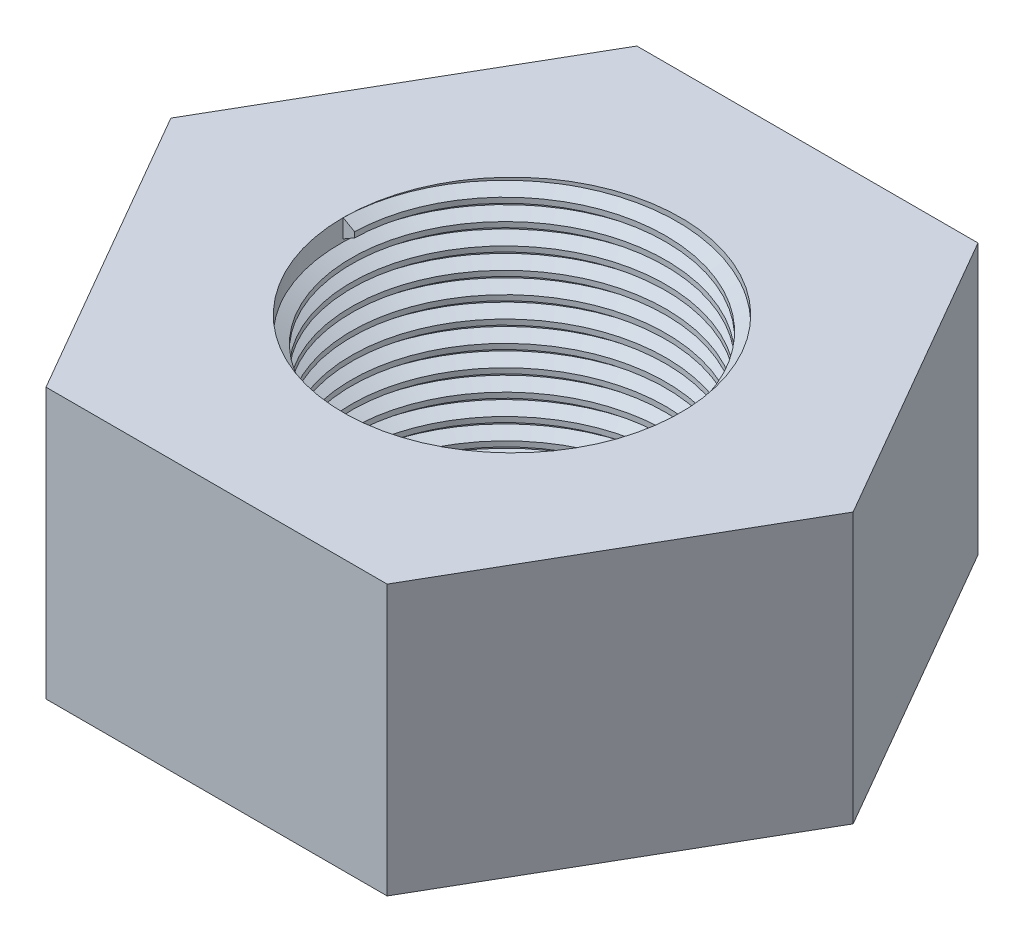
SolidWorks part; units mm, degrees
ref_plane "Ebene vorne" through (0, 0, 0) normal (0, 0, 1) x (1, 0, 0)
ref_plane "Ebene oben" through (0, 0, 0) normal (0, 1, 0) x (1, 0, 0)
ref_plane "Ebene rechts" through (0, 0, 0) normal (1, 0, 0) x (0, 0, -1)
sketch "Skizze1" plane through (0, 0, 0) normal (0, 1, 0) x (1, 0, 0)
  line L1 (4.0415, 0) -> (2.0207, 3.5)
  line L2 (2.0207, 3.5) -> (-2.0207, 3.5)
  line L3 (-2.0207, 3.5) -> (-4.0415, 0)
  line L4 (-4.0415, 0) -> (-2.0207, -3.5)
  line L5 (-2.0207, -3.5) -> (2.0207, -3.5)
  line L6 (2.0207, -3.5) -> (4.0415, 0)
  circle A0 centre (0, 0) radius 3.5 construction
  point P1 (0, 0)
  dimension "D1" = 7
extrude "Aufsatz-Linear austragen1" add sketch "Skizze1" along normal blind 3.2
sketch "Skizze2" plane through (0, 3.2, 0) normal (0, 1, 0) x (1, 0, 0)
  circle A0 centre (0, 0) radius 2
  dimension "D1" = 4
extrude "Schnitt-Linear austragen1" cut sketch "Skizze2" against normal up to surface (3.2 mm away) up to face at (0, 0, 0)
thread "Gewinde1" pitch 0.25 method extrude profile "Gewindeprofil1" start angle 0, offset 0, length 0, pitch 0.25, diameter 4
ref_plane "Ebene4" through (-2, 3.2, 0) normal (0, 0, 1) x (-1, 0, 0)
sketch "Gewindeprofil1" plane through (-2, 3.2, 0) normal (0, 0, 1) x (-1, 0, 0)
  line L0 (0, 0) -> (0, 0.25) construction
  line L11 (0, 0) -> (0, 0.2187)
  line L12 (0, 0.2187) -> (-0.1353, 0.1406)
  line L13 (-0.1353, 0.1406) -> (-0.1353, 0.0781)
  line L15 (-0.1353, 0.0781) -> (0, 0)
  line L17 (-0.1353, 0.1094) -> (0, 0.1094) construction
  point P2 (0, 0)
  dimension "Pitch" = 0.25
  dimension "Profile_Angle" = 60
  dimension "Profile_Land" = 0.0625
  dimension "Profile_Height" = 0.1353
